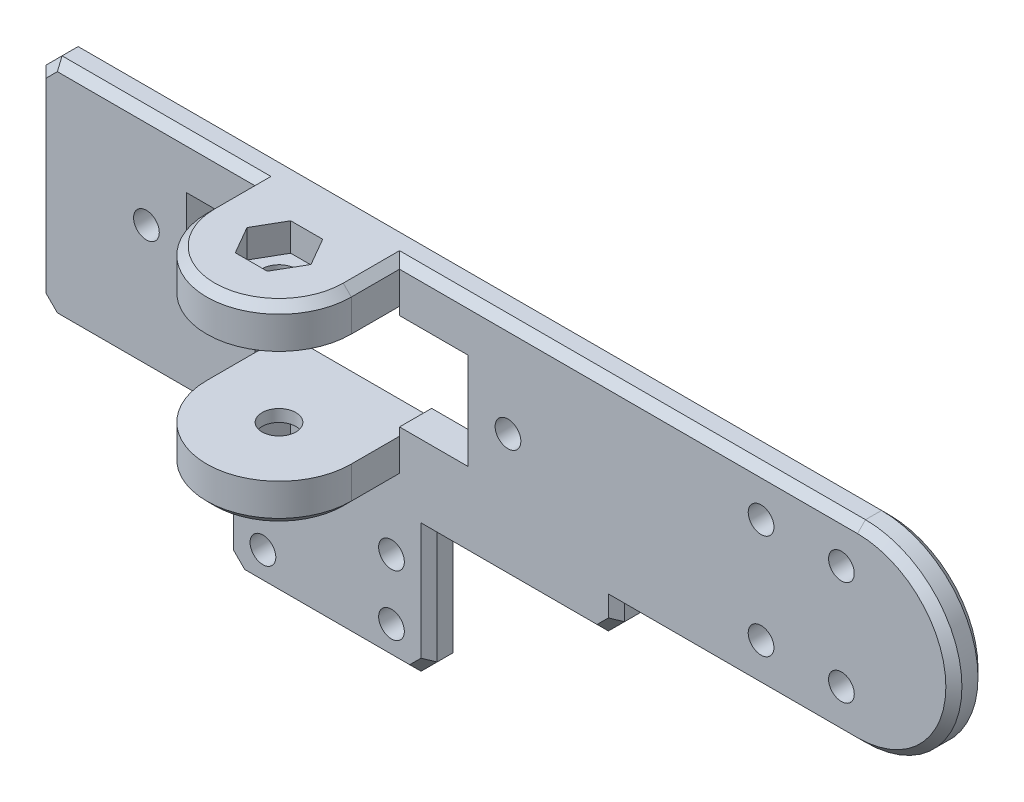
SolidWorks part; units mm, degrees
ref_plane "Alzado" through (0, 0, 0) normal (0, 0, 1) x (1, 0, 0)
ref_plane "Planta" through (0, 0, 0) normal (0, 1, 0) x (1, 0, 0)
ref_plane "Vista lateral" through (0, 0, 0) normal (1, 0, 0) x (0, 0, -1)
sketch "Croquis1" plane through (0, 0, 0) normal (0, 0, 1) x (1, 0, 0)
  line L0 (0, 0) -> (0, 18835.1574) construction
  line L1 (0, 0) -> (-18835.1574, 0) construction
  line L3 (-36, -12) -> (36, -12)
  line L4 (-36, -12) -> (-36, 12)
  line L5 (-36, 12) -> (36, 12)
  line L6 (36, -12) -> (36, 12)
  line L7 (-36, -12) -> (36, 12) construction
  line L8 (-36, 12) -> (36, -12) construction
  line L9 (-17.5, 6) -> (17.5, 6)
  line L10 (-17.5, 6) -> (-17.5, -6)
  line L11 (-17.5, -6) -> (17.5, -6)
  line L12 (17.5, 6) -> (17.5, -6)
  line L13 (-17.5, 6) -> (17.5, -6) construction
  line L14 (-17.5, -6) -> (17.5, 6) construction
  circle A0 centre (-22.5, 0) radius 1.6
  circle A1 centre (22.5, 0) radius 1.6
  point P7 (0, 0)
  point P16 (0, 0)
  dimension "D1" = 3.2
  dimension "D2" = 45
  dimension "D3" = 24
  dimension "D4" = 13.5
  dimension "D5" = 35
  dimension "D6" = 12
extrude "Saliente-Extruir1" add sketch "Croquis1" along normal blind 4
sketch "Croquis2" plane through (0, -12, 0) normal (0, -1, 0) x (1, 0, 0)
  line L0 (0, 0) -> (0, 50000) construction
  line L1 (0, -10) -> (-50000, -10) construction
  line L2 (-5, -10) -> (-5, -4)
  line L3 (-5, -4) -> (-36, -4)
  line L4 (-36, -4) -> (-36, 4)
  line L5 (-36, 4) -> (36, 4)
  line L6 (36, 4) -> (36, -4)
  line L7 (36, -4) -> (5, -4)
  line L8 (5, -4) -> (5, -10)
  line L9 (-36, 0) -> (36, 0) construction
  circle A0 centre (0, -10) radius 3.125
  arc A1 (-5, -10) -> (5, -10) centre (0, -10) ccw
  dimension "D2" = 6.25
  dimension "D3" = 4
  dimension "D4" = 5
  dimension "D1" = 10
extrude "Saliente-Extruir2" add sketch "Croquis2" along normal blind 4
sketch "Croquis3" plane through (0, 0, 0) normal (0, 0, -1) x (-1, 0, 0)
  line L0 (0, 0) -> (-50000, 0) construction
  line L1 (-66, 12) -> (-36, 12)
  line L2 (-66, -12) -> (-36, -12)
  line L3 (-36, -12) -> (-36, 12)
  arc A0 (-66, 12) -> (-66, -12) centre (-66, 0) ccw
  circle A1 centre (-54, 6.5) radius 1.6
  circle A2 centre (-64, 6.5) radius 1.6
  circle A3 centre (-54, -6.5) radius 1.6
  circle A4 centre (-64, -6.5) radius 1.6
  dimension "D1" = 30
  dimension "D2" = 3.2
  dimension "D5" = 28
  dimension "D3" = 13
  dimension "D4" = 18
extrude "Saliente-Extruir3" add sketch "Croquis3" against normal blind 4
sketch "Croquis5" plane through (0, 12, 0) normal (0, 1, 0) x (1, 0, 0)
  line L0 (0, 0) -> (0, 50000) construction
  line L1 (-9, -10) -> (-9, -4)
  line L2 (66, -4) -> (-36, -4) construction
  line L3 (-9, -4) -> (9, -4)
  line L4 (9, -4) -> (9, -10)
  line L5 (66, 0) -> (-36, 0) construction
  circle A0 centre (0, -10) radius 2.1
  arc A1 (-9, -10) -> (9, -10) centre (0, -10) ccw
  dimension "D1" = 10
  dimension "D2" = 9
  dimension "D3" = 4.2
extrude "Saliente-Extruir4" add sketch "Croquis5" against normal blind 5
sketch "Croquis6" plane through (0, 12, 0) normal (0, 1, 0) x (1, 0, 0)
  line L1 (3.9823, -10) -> (1.9912, -6.5512)
  line L2 (1.9912, -6.5512) -> (-1.9912, -6.5512)
  line L3 (-1.9912, -6.5512) -> (-3.9823, -10)
  line L4 (-3.9823, -10) -> (-1.9912, -13.4488)
  line L5 (-1.9912, -13.4488) -> (1.9912, -13.4488)
  line L6 (1.9912, -13.4488) -> (3.9823, -10)
  circle A0 centre (0, -10) radius 3.4488 construction
  dimension "D1" = 6.8976
extrude "Cortar-Extruir1" cut sketch "Croquis6" against normal blind 3.5
mirror "Simetría1" about plane through (0, 0, 0) normal (0, 1, 0) of "Cortar-Extruir1", "Saliente-Extruir4"
fillet "Redondeo1" radius 3 1 edges at (0, -12, 0)
sketch "Croquis7" plane through (0, 0, 4) normal (0, 0, 1) x (1, 0, 0)
  line L0 (0, 0) -> (0, 50000) construction
  line L1 (36, -16) -> (-36, -16) construction
  line L2 (-12.6808, -32) -> (12.6808, -32)
  line L3 (-12.6808, -32) -> (-12.6808, -16)
  line L4 (-12.6808, -16) -> (12.6808, -16)
  line L5 (12.6808, -32) -> (12.6808, -16)
  line L6 (-12.6808, -32) -> (12.6808, -16) construction
  line L7 (-12.6808, -16) -> (12.6808, -32) construction
  line L8 (0, -24) -> (50000, -24) construction
  circle A0 centre (-8, -20.25) radius 1.6
  circle A1 centre (8, -20.25) radius 1.6
  circle A2 centre (8, -27.75) radius 1.6
  circle A3 centre (-8, -27.75) radius 1.6
  point P3 (0, -24)
  dimension "D1" = 7.5
  dimension "D2" = 3.2
  dimension "D4" = 16
  dimension "D3" = 16
extrude "Saliente-Extruir5" add sketch "Croquis7" against normal blind 4
chamfer "Chaflán1" distance 2 angle 45 5 edges at (-36, 12, 2) (-36, -16, 0) (36, -16, 0) (-12.6808, -32, 2) (12.6808, -32, 2)
chamfer "Chaflán2" distance 1 angle 45 29 edges at (12.6808, -23, 0) (0, -32, 0) (-11.6808, -31, 0) (-12.6808, -23, 0) (36, -13, 4) (35, -15, 4) (23.3404, -16, 4) (12.6808, -23, 4) (11.6808, -31, 4) (0, -32, 4) (-11.6808, -31, 4) (-12.6808, -23, 4) (-23.3404, -16, 4) (-35, -15, 4) (-36, -2, 4) (-35, 11, 4) (-21.5, 12, 4) (16, 12, 0) (51, -12, 0) (78, 0, 0) (37.5, 12, 4) (51, -12, 4) (78, 0, 4) (-9, -12, 7) (9, -12, 7) (0, -12, 19) (-9, 12, 7) (9, 12, 7) (0, 12, 19)
sketch "Croquis8" plane through (0, 0, 4) normal (0, 0, 1) x (1, 0, 0)
  line L0 (-22.5, 0) -> (49977.5, 0) construction
  line L1 (-9, -7) -> (9, -7)
  line L2 (-9, -7) -> (-9, 7)
  line L3 (-9, 7) -> (9, 7)
  line L4 (9, -7) -> (9, 7)
  line L5 (-9, -7) -> (9, 7) construction
  line L6 (-9, 7) -> (9, -7) construction
  point P0 (0, 0)
extrude "Cortar-Extruir2" cut sketch "Croquis8" against normal through all
sketch "Croquis9" plane through (-36, 0, 0) normal (-1, 0, 0) x (0, 0, 1)
  line L1 (-19.0692, -7.9516) -> (0, -7.9516)
  line L2 (-19.0692, -7.9516) -> (-19.0692, -16)
  line L3 (-19.0692, -16) -> (0, -16)
  line L4 (0, -7.9516) -> (0, -16)
  line L5 (-19.0692, -7.9516) -> (0, -16) construction
  line L6 (-19.0692, -16) -> (0, -7.9516) construction
  point P4 (-9.5346, -11.9758)
extrude "Cortar-Extruir3" cut sketch "Croquis9" against normal through all
